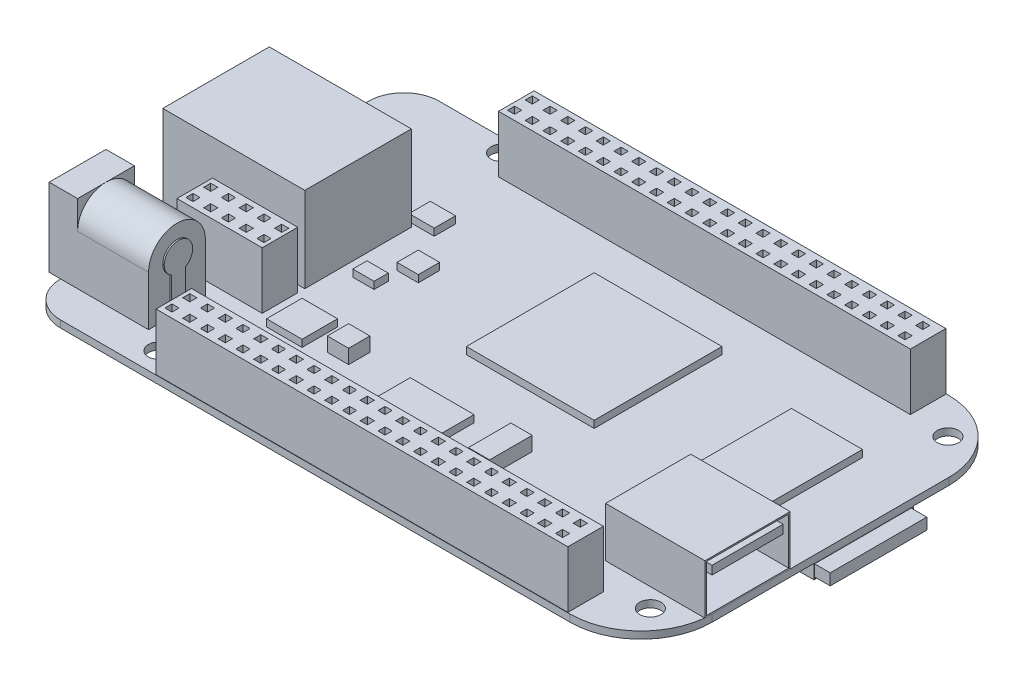
SolidWorks part; units mm, degrees
material "ABS"
ref_plane "Front" through (0, 0, 0) normal (0, 0, 1) x (1, 0, 0)
ref_plane "Top" through (0, 0, 0) normal (0, 1, 0) x (1, 0, 0)
ref_plane "Right" through (0, 0, 0) normal (1, 0, 0) x (0, 0, -1)
sketch "Sketch1" plane through (0, 0, 0) normal (0, 1, 0) x (1, 0, 0)
  line L0 (-38.5707, -26.67) -> (33.18, -26.67)
  line L1 (-27.8969, -23.495) -> (-27.8969, 24.765) construction
  line L2 (43.18, -16.67) -> (43.18, 16.67)
  line L3 (33.18, 26.67) -> (-38.5707, 26.67)
  line L4 (-43.5707, 21.67) -> (-43.5707, -21.67)
  line L5 (-27.8969, 24.765) -> (38.1431, 24.765) construction
  line L6 (38.1431, 24.765) -> (38.1431, 21.59) construction
  line L7 (-27.8969, -23.495) -> (38.1431, -23.495) construction
  line L8 (38.1431, -23.495) -> (38.1431, -20.32) construction
  arc A0 (43.18, 16.67) -> (33.18, 26.67) centre (33.18, 16.67) ccw
  arc A1 (33.18, -26.67) -> (43.18, -16.67) centre (33.18, -16.67) ccw
  arc A2 (-38.5707, -26.67) -> (-43.5707, -21.67) centre (-38.5707, -21.67) cw
  arc A3 (-43.5707, 21.67) -> (-38.5707, 26.67) centre (-38.5707, 21.67) cw
  circle A4 centre (38.1431, -20.32) radius 1.5
  circle A5 centre (38.1431, 21.59) radius 1.5
  circle A6 centre (-27.8969, -23.495) radius 1.5
  circle A7 centre (-27.8969, 24.765) radius 1.5
  dimension "D1" = 5
  dimension "D5" = 66.04
  dimension "D2" = 48.26
  dimension "D3" = 66.04
  dimension "D4" = 3.175
  dimension "D6" = 3.175
  dimension "D7" = 3.175
extrude "Boss-Extrude3" add sketch "Sketch1" along normal blind 1
sketch "Sketch2" plane through (0, 1, 0) normal (0, 1, 0) x (1, 0, 0)
  line L0 (-25.18, -6.67) -> (-37.18, -6.67)
  line L1 (-25.18, -6.67) -> (-25.18, -11.67)
  line L2 (32.82, -26.62) -> (-25.18, -26.62)
  line L3 (-37.18, -6.67) -> (-37.18, -11.67)
  line L4 (-37.18, -11.67) -> (-25.18, -11.67)
  line L5 (-25.18, -26.62) -> (-25.18, -21.62)
  line L8 (-25.18, -21.62) -> (32.82, -21.62)
  line L9 (32.82, -21.62) -> (32.82, -26.62)
  line L12 (-25.18, 26.62) -> (-25.18, 21.62)
  line L13 (32.82, 26.62) -> (-25.18, 26.62)
  line L14 (32.82, 21.62) -> (32.82, 26.62)
  line L15 (-25.18, 21.62) -> (32.82, 21.62)
extrude "Boss-Extrude5" add sketch "Sketch2" along normal blind 8
sketch "Sketch3" plane through (0, 9, 0) normal (0, 1, 0) x (1, 0, 0)
  line L3 (-22.18, 25.87) -> (-21.18, 25.87)
  line L4 (-22.18, -22.37) -> (-21.18, -22.37)
  line L5 (-24.68, 25.87) -> (-23.68, 25.87)
  line L6 (-21.18, 25.87) -> (-21.18, 24.87)
  line L7 (-23.68, 25.87) -> (-23.68, 24.87)
  line L8 (-23.68, 24.87) -> (-24.68, 24.87)
  line L9 (-24.68, 24.87) -> (-24.68, 25.87)
  line L10 (-21.18, 24.87) -> (-22.18, 24.87)
  line L11 (-22.18, 24.87) -> (-22.18, 25.87)
  line L12 (-19.68, 25.87) -> (-18.68, 25.87)
  line L13 (-18.68, 25.87) -> (-18.68, 24.87)
  line L14 (-18.68, 24.87) -> (-19.68, 24.87)
  line L15 (-19.68, 24.87) -> (-19.68, 25.87)
  line L16 (-17.18, 25.87) -> (-16.18, 25.87)
  line L17 (-16.18, 25.87) -> (-16.18, 24.87)
  line L18 (-16.18, 24.87) -> (-17.18, 24.87)
  line L19 (-17.18, 24.87) -> (-17.18, 25.87)
  line L20 (-14.68, 25.87) -> (-13.68, 25.87)
  line L21 (-13.68, 25.87) -> (-13.68, 24.87)
  line L22 (-13.68, 24.87) -> (-14.68, 24.87)
  line L23 (-14.68, 24.87) -> (-14.68, 25.87)
  line L24 (-12.18, 25.87) -> (-11.18, 25.87)
  line L25 (-11.18, 25.87) -> (-11.18, 24.87)
  line L26 (-11.18, 24.87) -> (-12.18, 24.87)
  line L27 (-12.18, 24.87) -> (-12.18, 25.87)
  line L28 (-9.68, 25.87) -> (-8.68, 25.87)
  line L29 (-8.68, 25.87) -> (-8.68, 24.87)
  line L30 (-8.68, 24.87) -> (-9.68, 24.87)
  line L31 (-9.68, 24.87) -> (-9.68, 25.87)
  line L32 (-7.18, 25.87) -> (-6.18, 25.87)
  line L33 (-6.18, 25.87) -> (-6.18, 24.87)
  line L34 (-6.18, 24.87) -> (-7.18, 24.87)
  line L35 (-7.18, 24.87) -> (-7.18, 25.87)
  line L36 (-4.68, 25.87) -> (-3.68, 25.87)
  line L37 (-3.68, 25.87) -> (-3.68, 24.87)
  line L38 (-3.68, 24.87) -> (-4.68, 24.87)
  line L39 (-4.68, 24.87) -> (-4.68, 25.87)
  line L40 (-2.18, 25.87) -> (-1.18, 25.87)
  line L41 (-1.18, 25.87) -> (-1.18, 24.87)
  line L42 (-1.18, 24.87) -> (-2.18, 24.87)
  line L43 (-2.18, 24.87) -> (-2.18, 25.87)
  line L44 (0.32, 25.87) -> (1.32, 25.87)
  line L45 (1.32, 25.87) -> (1.32, 24.87)
  line L46 (1.32, 24.87) -> (0.32, 24.87)
  line L47 (0.32, 24.87) -> (0.32, 25.87)
  line L48 (2.82, 25.87) -> (3.82, 25.87)
  line L49 (3.82, 25.87) -> (3.82, 24.87)
  line L50 (3.82, 24.87) -> (2.82, 24.87)
  line L51 (2.82, 24.87) -> (2.82, 25.87)
  line L52 (5.32, 25.87) -> (6.32, 25.87)
  line L53 (6.32, 25.87) -> (6.32, 24.87)
  line L54 (6.32, 24.87) -> (5.32, 24.87)
  line L55 (5.32, 24.87) -> (5.32, 25.87)
  line L56 (7.82, 25.87) -> (8.82, 25.87)
  line L57 (8.82, 25.87) -> (8.82, 24.87)
  line L58 (8.82, 24.87) -> (7.82, 24.87)
  line L59 (7.82, 24.87) -> (7.82, 25.87)
  line L60 (10.32, 25.87) -> (11.32, 25.87)
  line L61 (11.32, 25.87) -> (11.32, 24.87)
  line L62 (11.32, 24.87) -> (10.32, 24.87)
  line L63 (10.32, 24.87) -> (10.32, 25.87)
  line L64 (12.82, 25.87) -> (13.82, 25.87)
  line L65 (13.82, 25.87) -> (13.82, 24.87)
  line L66 (13.82, 24.87) -> (12.82, 24.87)
  line L67 (12.82, 24.87) -> (12.82, 25.87)
  line L68 (15.32, 25.87) -> (16.32, 25.87)
  line L69 (16.32, 25.87) -> (16.32, 24.87)
  line L70 (16.32, 24.87) -> (15.32, 24.87)
  line L71 (15.32, 24.87) -> (15.32, 25.87)
  line L72 (17.82, 25.87) -> (18.82, 25.87)
  line L73 (18.82, 25.87) -> (18.82, 24.87)
  line L74 (18.82, 24.87) -> (17.82, 24.87)
  line L75 (17.82, 24.87) -> (17.82, 25.87)
  line L76 (20.32, 25.87) -> (21.32, 25.87)
  line L77 (21.32, 25.87) -> (21.32, 24.87)
  line L78 (21.32, 24.87) -> (20.32, 24.87)
  line L79 (20.32, 24.87) -> (20.32, 25.87)
  line L80 (22.82, 25.87) -> (23.82, 25.87)
  line L81 (23.82, 25.87) -> (23.82, 24.87)
  line L82 (23.82, 24.87) -> (22.82, 24.87)
  line L83 (22.82, 24.87) -> (22.82, 25.87)
  line L84 (25.32, 25.87) -> (26.32, 25.87)
  line L85 (26.32, 25.87) -> (26.32, 24.87)
  line L86 (26.32, 24.87) -> (25.32, 24.87)
  line L87 (25.32, 24.87) -> (25.32, 25.87)
  line L88 (27.82, 25.87) -> (28.82, 25.87)
  line L89 (28.82, 25.87) -> (28.82, 24.87)
  line L90 (28.82, 24.87) -> (27.82, 24.87)
  line L91 (27.82, 24.87) -> (27.82, 25.87)
  line L92 (30.32, 25.87) -> (31.32, 25.87)
  line L93 (31.32, 25.87) -> (31.32, 24.87)
  line L94 (31.32, 24.87) -> (30.32, 24.87)
  line L95 (30.32, 24.87) -> (30.32, 25.87)
  line L96 (-18.68, 23.37) -> (-19.68, 23.37)
  line L97 (-21.18, 23.37) -> (-22.18, 23.37)
  line L98 (-23.68, 23.37) -> (-24.68, 23.37)
  line L99 (31.32, 23.37) -> (30.32, 23.37)
  line L100 (28.82, 23.37) -> (27.82, 23.37)
  line L101 (26.32, 23.37) -> (25.32, 23.37)
  line L102 (23.82, 23.37) -> (22.82, 23.37)
  line L103 (21.32, 23.37) -> (20.32, 23.37)
  line L104 (18.82, 23.37) -> (17.82, 23.37)
  line L105 (16.32, 23.37) -> (15.32, 23.37)
  line L106 (13.82, 23.37) -> (12.82, 23.37)
  line L107 (11.32, 23.37) -> (10.32, 23.37)
  line L108 (8.82, 23.37) -> (7.82, 23.37)
  line L109 (6.32, 23.37) -> (5.32, 23.37)
  line L110 (3.82, 23.37) -> (2.82, 23.37)
  line L111 (1.32, 23.37) -> (0.32, 23.37)
  line L112 (-1.18, 23.37) -> (-2.18, 23.37)
  line L113 (-3.68, 23.37) -> (-4.68, 23.37)
  line L114 (-6.18, 23.37) -> (-7.18, 23.37)
  line L115 (-8.68, 23.37) -> (-9.68, 23.37)
  line L116 (-11.18, 23.37) -> (-12.18, 23.37)
  line L117 (-13.68, 23.37) -> (-14.68, 23.37)
  line L118 (-16.18, 23.37) -> (-17.18, 23.37)
  line L119 (30.32, 23.37) -> (30.32, 22.37)
  line L120 (31.32, 22.37) -> (31.32, 23.37)
  line L121 (30.32, 22.37) -> (31.32, 22.37)
  line L122 (27.82, 23.37) -> (27.82, 22.37)
  line L123 (28.82, 22.37) -> (28.82, 23.37)
  line L124 (27.82, 22.37) -> (28.82, 22.37)
  line L125 (25.32, 23.37) -> (25.32, 22.37)
  line L126 (26.32, 22.37) -> (26.32, 23.37)
  line L127 (25.32, 22.37) -> (26.32, 22.37)
  line L128 (22.82, 23.37) -> (22.82, 22.37)
  line L129 (23.82, 22.37) -> (23.82, 23.37)
  line L130 (22.82, 22.37) -> (23.82, 22.37)
  line L131 (20.32, 23.37) -> (20.32, 22.37)
  line L132 (21.32, 22.37) -> (21.32, 23.37)
  line L133 (20.32, 22.37) -> (21.32, 22.37)
  line L134 (17.82, 23.37) -> (17.82, 22.37)
  line L135 (18.82, 22.37) -> (18.82, 23.37)
  line L136 (17.82, 22.37) -> (18.82, 22.37)
  line L137 (15.32, 23.37) -> (15.32, 22.37)
  line L138 (16.32, 22.37) -> (16.32, 23.37)
  line L139 (15.32, 22.37) -> (16.32, 22.37)
  line L140 (12.82, 23.37) -> (12.82, 22.37)
  line L141 (13.82, 22.37) -> (13.82, 23.37)
  line L142 (12.82, 22.37) -> (13.82, 22.37)
  line L143 (10.32, 23.37) -> (10.32, 22.37)
  line L144 (11.32, 22.37) -> (11.32, 23.37)
  line L145 (10.32, 22.37) -> (11.32, 22.37)
  line L146 (7.82, 23.37) -> (7.82, 22.37)
  line L147 (8.82, 22.37) -> (8.82, 23.37)
  line L148 (7.82, 22.37) -> (8.82, 22.37)
  line L149 (5.32, 23.37) -> (5.32, 22.37)
  line L150 (6.32, 22.37) -> (6.32, 23.37)
  line L151 (5.32, 22.37) -> (6.32, 22.37)
  line L152 (2.82, 23.37) -> (2.82, 22.37)
  line L153 (3.82, 22.37) -> (3.82, 23.37)
  line L154 (2.82, 22.37) -> (3.82, 22.37)
  line L155 (0.32, 23.37) -> (0.32, 22.37)
  line L156 (1.32, 22.37) -> (1.32, 23.37)
  line L157 (0.32, 22.37) -> (1.32, 22.37)
  line L158 (-2.18, 23.37) -> (-2.18, 22.37)
  line L159 (-1.18, 22.37) -> (-1.18, 23.37)
  line L160 (-2.18, 22.37) -> (-1.18, 22.37)
  line L161 (-4.68, 23.37) -> (-4.68, 22.37)
  line L162 (-3.68, 22.37) -> (-3.68, 23.37)
  line L163 (-4.68, 22.37) -> (-3.68, 22.37)
  line L164 (-7.18, 23.37) -> (-7.18, 22.37)
  line L165 (-6.18, 22.37) -> (-6.18, 23.37)
  line L166 (-7.18, 22.37) -> (-6.18, 22.37)
  line L167 (-9.68, 23.37) -> (-9.68, 22.37)
  line L168 (-8.68, 22.37) -> (-8.68, 23.37)
  line L169 (-9.68, 22.37) -> (-8.68, 22.37)
  line L170 (-12.18, 23.37) -> (-12.18, 22.37)
  line L171 (-11.18, 22.37) -> (-11.18, 23.37)
  line L172 (-12.18, 22.37) -> (-11.18, 22.37)
  line L173 (-14.68, 23.37) -> (-14.68, 22.37)
  line L174 (-13.68, 22.37) -> (-13.68, 23.37)
  line L175 (-14.68, 22.37) -> (-13.68, 22.37)
  line L176 (-17.18, 23.37) -> (-17.18, 22.37)
  line L177 (-16.18, 22.37) -> (-16.18, 23.37)
  line L178 (-17.18, 22.37) -> (-16.18, 22.37)
  line L179 (-19.68, 23.37) -> (-19.68, 22.37)
  line L180 (-18.68, 22.37) -> (-18.68, 23.37)
  line L181 (-19.68, 22.37) -> (-18.68, 22.37)
  line L182 (-22.18, 23.37) -> (-22.18, 22.37)
  line L183 (-24.68, 23.37) -> (-24.68, 22.37)
  line L184 (-23.68, 22.37) -> (-23.68, 23.37)
  line L185 (-21.18, 22.37) -> (-21.18, 23.37)
  line L186 (-24.68, 22.37) -> (-23.68, 22.37)
  line L187 (-22.18, 22.37) -> (-21.18, 22.37)
  line L188 (-24.68, -22.37) -> (-23.68, -22.37)
  line L189 (-21.18, -22.37) -> (-21.18, -23.37)
  line L190 (-23.68, -22.37) -> (-23.68, -23.37)
  line L191 (-24.68, -23.37) -> (-24.68, -22.37)
  line L192 (-22.18, -23.37) -> (-22.18, -22.37)
  line L193 (-19.68, -22.37) -> (-18.68, -22.37)
  line L194 (-18.68, -22.37) -> (-18.68, -23.37)
  line L195 (-19.68, -23.37) -> (-19.68, -22.37)
  line L196 (-17.18, -22.37) -> (-16.18, -22.37)
  line L197 (-16.18, -22.37) -> (-16.18, -23.37)
  line L198 (-17.18, -23.37) -> (-17.18, -22.37)
  line L199 (-14.68, -22.37) -> (-13.68, -22.37)
  line L200 (-13.68, -22.37) -> (-13.68, -23.37)
  line L201 (-14.68, -23.37) -> (-14.68, -22.37)
  line L202 (-12.18, -22.37) -> (-11.18, -22.37)
  line L203 (-11.18, -22.37) -> (-11.18, -23.37)
  line L204 (-12.18, -23.37) -> (-12.18, -22.37)
  line L205 (-9.68, -22.37) -> (-8.68, -22.37)
  line L206 (-8.68, -22.37) -> (-8.68, -23.37)
  line L207 (-9.68, -23.37) -> (-9.68, -22.37)
  line L208 (-7.18, -22.37) -> (-6.18, -22.37)
  line L209 (-6.18, -22.37) -> (-6.18, -23.37)
  line L210 (-7.18, -23.37) -> (-7.18, -22.37)
  line L211 (-4.68, -22.37) -> (-3.68, -22.37)
  line L212 (-3.68, -22.37) -> (-3.68, -23.37)
  line L213 (-4.68, -23.37) -> (-4.68, -22.37)
  line L214 (-2.18, -22.37) -> (-1.18, -22.37)
  line L215 (-1.18, -22.37) -> (-1.18, -23.37)
  line L216 (-2.18, -23.37) -> (-2.18, -22.37)
  line L217 (0.32, -22.37) -> (1.32, -22.37)
  line L218 (1.32, -22.37) -> (1.32, -23.37)
  line L219 (0.32, -23.37) -> (0.32, -22.37)
  line L220 (2.82, -22.37) -> (3.82, -22.37)
  line L221 (3.82, -22.37) -> (3.82, -23.37)
  line L222 (2.82, -23.37) -> (2.82, -22.37)
  line L223 (5.32, -22.37) -> (6.32, -22.37)
  line L224 (6.32, -22.37) -> (6.32, -23.37)
  line L225 (5.32, -23.37) -> (5.32, -22.37)
  line L226 (7.82, -22.37) -> (8.82, -22.37)
  line L227 (8.82, -22.37) -> (8.82, -23.37)
  line L228 (7.82, -23.37) -> (7.82, -22.37)
  line L229 (10.32, -22.37) -> (11.32, -22.37)
  line L230 (11.32, -22.37) -> (11.32, -23.37)
  line L231 (10.32, -23.37) -> (10.32, -22.37)
  line L232 (12.82, -22.37) -> (13.82, -22.37)
  line L233 (13.82, -22.37) -> (13.82, -23.37)
  line L234 (12.82, -23.37) -> (12.82, -22.37)
  line L235 (15.32, -22.37) -> (16.32, -22.37)
  line L236 (16.32, -22.37) -> (16.32, -23.37)
  line L237 (15.32, -23.37) -> (15.32, -22.37)
  line L238 (17.82, -22.37) -> (18.82, -22.37)
  line L239 (18.82, -22.37) -> (18.82, -23.37)
  line L240 (17.82, -23.37) -> (17.82, -22.37)
  line L241 (20.32, -22.37) -> (21.32, -22.37)
  line L242 (21.32, -22.37) -> (21.32, -23.37)
  line L243 (20.32, -23.37) -> (20.32, -22.37)
  line L244 (22.82, -22.37) -> (23.82, -22.37)
  line L245 (23.82, -22.37) -> (23.82, -23.37)
  line L246 (22.82, -23.37) -> (22.82, -22.37)
  line L247 (25.32, -22.37) -> (26.32, -22.37)
  line L248 (26.32, -22.37) -> (26.32, -23.37)
  line L249 (25.32, -23.37) -> (25.32, -22.37)
  line L250 (27.82, -22.37) -> (28.82, -22.37)
  line L251 (28.82, -22.37) -> (28.82, -23.37)
  line L252 (27.82, -23.37) -> (27.82, -22.37)
  line L253 (30.32, -22.37) -> (31.32, -22.37)
  line L254 (31.32, -22.37) -> (31.32, -23.37)
  line L255 (30.32, -23.37) -> (30.32, -22.37)
  line L256 (-16.18, -23.37) -> (-17.18, -23.37)
  line L257 (-13.68, -23.37) -> (-14.68, -23.37)
  line L258 (-11.18, -23.37) -> (-12.18, -23.37)
  line L259 (-8.68, -23.37) -> (-9.68, -23.37)
  line L260 (-6.18, -23.37) -> (-7.18, -23.37)
  line L261 (-3.68, -23.37) -> (-4.68, -23.37)
  line L262 (-1.18, -23.37) -> (-2.18, -23.37)
  line L263 (1.32, -23.37) -> (0.32, -23.37)
  line L264 (3.82, -23.37) -> (2.82, -23.37)
  line L265 (6.32, -23.37) -> (5.32, -23.37)
  line L266 (8.82, -23.37) -> (7.82, -23.37)
  line L267 (11.32, -23.37) -> (10.32, -23.37)
  line L268 (13.82, -23.37) -> (12.82, -23.37)
  line L269 (16.32, -23.37) -> (15.32, -23.37)
  line L270 (18.82, -23.37) -> (17.82, -23.37)
  line L271 (21.32, -23.37) -> (20.32, -23.37)
  line L272 (23.82, -23.37) -> (22.82, -23.37)
  line L273 (26.32, -23.37) -> (25.32, -23.37)
  line L274 (28.82, -23.37) -> (27.82, -23.37)
  line L275 (31.32, -23.37) -> (30.32, -23.37)
  line L276 (-23.68, -23.37) -> (-24.68, -23.37)
  line L277 (-21.18, -23.37) -> (-22.18, -23.37)
  line L278 (-18.68, -23.37) -> (-19.68, -23.37)
  line L279 (30.32, -24.87) -> (30.32, -25.87)
  line L280 (31.32, -24.87) -> (30.32, -24.87)
  line L281 (31.32, -25.87) -> (31.32, -24.87)
  line L282 (30.32, -25.87) -> (31.32, -25.87)
  line L283 (27.82, -24.87) -> (27.82, -25.87)
  line L284 (28.82, -24.87) -> (27.82, -24.87)
  line L285 (28.82, -25.87) -> (28.82, -24.87)
  line L286 (27.82, -25.87) -> (28.82, -25.87)
  line L287 (25.32, -24.87) -> (25.32, -25.87)
  line L288 (26.32, -24.87) -> (25.32, -24.87)
  line L289 (26.32, -25.87) -> (26.32, -24.87)
  line L290 (25.32, -25.87) -> (26.32, -25.87)
  line L291 (22.82, -24.87) -> (22.82, -25.87)
  line L292 (23.82, -24.87) -> (22.82, -24.87)
  line L293 (23.82, -25.87) -> (23.82, -24.87)
  line L294 (22.82, -25.87) -> (23.82, -25.87)
  line L295 (20.32, -24.87) -> (20.32, -25.87)
  line L296 (21.32, -24.87) -> (20.32, -24.87)
  line L297 (21.32, -25.87) -> (21.32, -24.87)
  line L298 (20.32, -25.87) -> (21.32, -25.87)
  line L299 (17.82, -24.87) -> (17.82, -25.87)
  line L300 (18.82, -24.87) -> (17.82, -24.87)
  line L301 (18.82, -25.87) -> (18.82, -24.87)
  line L302 (17.82, -25.87) -> (18.82, -25.87)
  line L303 (15.32, -24.87) -> (15.32, -25.87)
  line L304 (16.32, -24.87) -> (15.32, -24.87)
  line L305 (16.32, -25.87) -> (16.32, -24.87)
  line L306 (15.32, -25.87) -> (16.32, -25.87)
  line L307 (12.82, -24.87) -> (12.82, -25.87)
  line L308 (13.82, -24.87) -> (12.82, -24.87)
  line L309 (13.82, -25.87) -> (13.82, -24.87)
  line L310 (12.82, -25.87) -> (13.82, -25.87)
  line L311 (10.32, -24.87) -> (10.32, -25.87)
  line L312 (11.32, -24.87) -> (10.32, -24.87)
  line L313 (11.32, -25.87) -> (11.32, -24.87)
  line L314 (10.32, -25.87) -> (11.32, -25.87)
  line L315 (7.82, -24.87) -> (7.82, -25.87)
  line L316 (8.82, -24.87) -> (7.82, -24.87)
  line L317 (8.82, -25.87) -> (8.82, -24.87)
  line L318 (7.82, -25.87) -> (8.82, -25.87)
  line L319 (5.32, -24.87) -> (5.32, -25.87)
  line L320 (6.32, -24.87) -> (5.32, -24.87)
  line L321 (6.32, -25.87) -> (6.32, -24.87)
  line L322 (5.32, -25.87) -> (6.32, -25.87)
  line L323 (2.82, -24.87) -> (2.82, -25.87)
  line L324 (3.82, -24.87) -> (2.82, -24.87)
  line L325 (3.82, -25.87) -> (3.82, -24.87)
  line L326 (2.82, -25.87) -> (3.82, -25.87)
  line L327 (0.32, -24.87) -> (0.32, -25.87)
  line L328 (1.32, -24.87) -> (0.32, -24.87)
  line L329 (1.32, -25.87) -> (1.32, -24.87)
  line L330 (0.32, -25.87) -> (1.32, -25.87)
  line L331 (-2.18, -24.87) -> (-2.18, -25.87)
  line L332 (-1.18, -24.87) -> (-2.18, -24.87)
  line L333 (-1.18, -25.87) -> (-1.18, -24.87)
  line L334 (-2.18, -25.87) -> (-1.18, -25.87)
  line L335 (-4.68, -24.87) -> (-4.68, -25.87)
  line L336 (-3.68, -24.87) -> (-4.68, -24.87)
  line L337 (-3.68, -25.87) -> (-3.68, -24.87)
  line L338 (-4.68, -25.87) -> (-3.68, -25.87)
  line L339 (-7.18, -24.87) -> (-7.18, -25.87)
  line L340 (-6.18, -24.87) -> (-7.18, -24.87)
  line L341 (-6.18, -25.87) -> (-6.18, -24.87)
  line L342 (-7.18, -25.87) -> (-6.18, -25.87)
  line L343 (-9.68, -24.87) -> (-9.68, -25.87)
  line L344 (-8.68, -24.87) -> (-9.68, -24.87)
  line L345 (-8.68, -25.87) -> (-8.68, -24.87)
  line L346 (-9.68, -25.87) -> (-8.68, -25.87)
  line L347 (-12.18, -24.87) -> (-12.18, -25.87)
  line L348 (-11.18, -24.87) -> (-12.18, -24.87)
  line L349 (-11.18, -25.87) -> (-11.18, -24.87)
  line L350 (-12.18, -25.87) -> (-11.18, -25.87)
  line L351 (-14.68, -24.87) -> (-14.68, -25.87)
  line L352 (-13.68, -24.87) -> (-14.68, -24.87)
  line L353 (-13.68, -25.87) -> (-13.68, -24.87)
  line L354 (-14.68, -25.87) -> (-13.68, -25.87)
  line L355 (-17.18, -24.87) -> (-17.18, -25.87)
  line L356 (-16.18, -24.87) -> (-17.18, -24.87)
  line L357 (-16.18, -25.87) -> (-16.18, -24.87)
  line L358 (-17.18, -25.87) -> (-16.18, -25.87)
  line L359 (-19.68, -24.87) -> (-19.68, -25.87)
  line L360 (-18.68, -24.87) -> (-19.68, -24.87)
  line L361 (-18.68, -25.87) -> (-18.68, -24.87)
  line L362 (-19.68, -25.87) -> (-18.68, -25.87)
  line L363 (-22.18, -24.87) -> (-22.18, -25.87)
  line L364 (-21.18, -24.87) -> (-22.18, -24.87)
  line L365 (-24.68, -24.87) -> (-24.68, -25.87)
  line L366 (-23.68, -24.87) -> (-24.68, -24.87)
  line L367 (-23.68, -25.87) -> (-23.68, -24.87)
  line L368 (-21.18, -25.87) -> (-21.18, -24.87)
  line L369 (-24.68, -25.87) -> (-23.68, -25.87)
  line L370 (-22.18, -25.87) -> (-21.18, -25.87)
  line L371 (-28.18, -10.92) -> (-29.18, -10.92)
  line L410 (-25.68, -10.92) -> (-26.68, -10.92)
  line L411 (-29.18, -10.92) -> (-29.18, -9.92)
  line L412 (-26.68, -10.92) -> (-26.68, -9.92)
  line L413 (-25.68, -9.92) -> (-25.68, -10.92)
  line L414 (-28.18, -9.92) -> (-28.18, -10.92)
  line L415 (-30.68, -10.92) -> (-31.68, -10.92)
  line L416 (-31.68, -10.92) -> (-31.68, -9.92)
  line L417 (-30.68, -9.92) -> (-30.68, -10.92)
  line L418 (-33.18, -10.92) -> (-34.18, -10.92)
  line L419 (-34.18, -10.92) -> (-34.18, -9.92)
  line L420 (-33.18, -9.92) -> (-33.18, -10.92)
  line L421 (-35.68, -10.92) -> (-36.68, -10.92)
  line L422 (-36.68, -10.92) -> (-36.68, -9.92)
  line L423 (-35.68, -9.92) -> (-35.68, -10.92)
  line L424 (-34.18, -9.92) -> (-33.18, -9.92)
  line L425 (-36.68, -9.92) -> (-35.68, -9.92)
  line L426 (-26.68, -9.92) -> (-25.68, -9.92)
  line L427 (-29.18, -9.92) -> (-28.18, -9.92)
  line L428 (-31.68, -9.92) -> (-30.68, -9.92)
  line L429 (-35.68, -8.42) -> (-35.68, -7.42)
  line L430 (-36.68, -8.42) -> (-35.68, -8.42)
  line L431 (-36.68, -7.42) -> (-36.68, -8.42)
  line L432 (-35.68, -7.42) -> (-36.68, -7.42)
  line L433 (-33.18, -8.42) -> (-33.18, -7.42)
  line L434 (-34.18, -8.42) -> (-33.18, -8.42)
  line L435 (-34.18, -7.42) -> (-34.18, -8.42)
  line L436 (-33.18, -7.42) -> (-34.18, -7.42)
  line L437 (-30.68, -8.42) -> (-30.68, -7.42)
  line L438 (-31.68, -8.42) -> (-30.68, -8.42)
  line L439 (-31.68, -7.42) -> (-31.68, -8.42)
  line L440 (-30.68, -7.42) -> (-31.68, -7.42)
  line L441 (-28.18, -8.42) -> (-28.18, -7.42)
  line L442 (-29.18, -8.42) -> (-28.18, -8.42)
  line L443 (-25.68, -8.42) -> (-25.68, -7.42)
  line L444 (-26.68, -8.42) -> (-25.68, -8.42)
  line L445 (-26.68, -7.42) -> (-26.68, -8.42)
  line L446 (-29.18, -7.42) -> (-29.18, -8.42)
  line L447 (-25.68, -7.42) -> (-26.68, -7.42)
  line L448 (-28.18, -7.42) -> (-29.18, -7.42)
  dimension "D1" = 23
extrude "Cut-Extrude2" cut sketch "Sketch3" against normal blind 7
sketch "Sketch4" plane through (0, 1, 0) normal (0, 1, 0) x (1, 0, 0)
  line L1 (-25.18, -5.67) -> (-45.18, -5.67)
  line L2 (-45.18, -5.67) -> (-45.18, 9.33)
  line L3 (-45.18, 9.33) -> (-25.18, 9.33)
  line L4 (-25.18, 9.33) -> (-25.18, -5.67)
extrude "Boss-Extrude6" add sketch "Sketch4" along normal blind 12
sketch "Sketch5" plane through (-45.18, 0, 0) normal (-1, 0, 0) x (0, 0, 1)
  line L3 (-4.33, 2) -> (-5.33, 2)
  line L4 (-5.33, 2) -> (-5.33, 4)
  line L5 (-5.33, 4) -> (-8.33, 4)
  line L6 (-8.33, 4) -> (-8.33, 11)
  line L7 (-8.33, 11) -> (4.67, 11)
  line L8 (-4.33, 2) -> (-4.33, 1.05)
  line L9 (0.67, 1.05) -> (0.67, 2)
  line L10 (4.67, 4) -> (4.67, 11)
  line L11 (1.67, 4) -> (4.67, 4)
  line L12 (1.67, 2) -> (1.67, 4)
  line L13 (0.67, 2) -> (1.67, 2)
  line L14 (-4.33, 1.05) -> (0.67, 1.05)
extrude "Cut-Extrude3" cut sketch "Sketch5" against normal blind 15
sketch "Sketch6" plane through (0, 1, 0) normal (0, 1, 0) x (1, 0, 0)
  line L0 (-31.18, -21.67) -> (-31.18, -13.67)
  line L1 (-31.18, -13.67) -> (-45.18, -13.67)
  line L2 (-31.18, -21.67) -> (-45.18, -21.67)
  line L3 (-45.18, -13.67) -> (-45.18, -21.67)
extrude "Boss-Extrude7" add sketch "Sketch6" along normal blind 11
sketch "Sketch8" plane through (-31.18, 0, 0) normal (1, 0, 0) x (0, 0, -1)
  line L1 (-13.67, 8) -> (-13.67, 12)
  line L2 (-13.67, 12) -> (-21.67, 12)
  line L3 (-21.67, 12) -> (-21.67, 8)
  arc A0 (-13.67, 8) -> (-21.67, 8) centre (-17.67, 8) ccw
  line M2 (-13.67, 1) -> (-13.67, 12)
  line M3 (-13.67, 12) -> (-21.67, 12)
  line M4 (-21.67, 12) -> (-21.67, 1)
extrude "Cut-Extrude5" cut sketch "Sketch8" against normal blind 10 contours A0 L2 M4 | A0 M2 M3 region at (-31.18, 11.1065, 14.5635) region at (-31.18, 11.1065, 20.7765)
sketch "Sketch9" plane through (-45.18, 0, 0) normal (-1, 0, 0) x (0, 0, 1)
  circle A0 centre (17.67, 8) radius 3
  circle A1 centre (17.67, 8) radius 0.2
extrude "Cut-Extrude6" cut sketch "Sketch9" against normal blind 10 contours A0 A1 region at (-45.18, 8, 14.7549)
sketch "Sketch10" plane through (0, 1, 0) normal (0, 1, 0) x (1, 0, 0)
  line L0 (43.18, -5.67) -> (29.18, -5.67)
  line L1 (43.18, -16.67) -> (43.18, 16.67) construction
  line L2 (43.18, -5.67) -> (43.18, -17.67)
  line L3 (29.18, -5.67) -> (29.18, -17.67)
  line L4 (29.18, -17.67) -> (43.18, -17.67)
extrude "Boss-Extrude9" add sketch "Sketch10" along normal blind 7 separate body
sketch "Sketch11" plane through (43.18, 0, 0) normal (1, 0, 0) x (0, 0, -1)
  line L0 (-17.47, 7.8) -> (-17.47, 1.2)
  line L1 (-5.87, 7.8) -> (-5.87, 1.2)
  line L3 (-16.67, 6.9526) -> (-16.67, 5.7526)
  line L4 (-16.67, 5.7526) -> (-6.67, 5.7526)
  line L5 (-6.67, 6.9526) -> (-16.67, 6.9526)
  line L6 (-6.67, 5.7526) -> (-6.67, 6.9526)
  line L7 (-17.47, 7.8) -> (-5.87, 7.8)
  line L10 (-17.47, 1.2) -> (-5.87, 1.2)
extrude "Cut-Extrude7" cut sketch "Sketch11" against normal blind 10 contours L0 L10 L1 L7 L6 L4 L3 L5 region at (43.18, 4.1557, 11.67)
sketch "Sketch12" plane through (0, 0, 0) normal (0, -1, 0) x (1, 0, 0)
  line L0 (43.18, 2.33) -> (43.18, -11.67)
  line L1 (43.18, -11.67) -> (28.18, -11.67)
  line L2 (43.18, 16.67) -> (43.18, -16.67) construction
  line L4 (28.18, -11.67) -> (28.18, 2.33)
  line L5 (28.18, 2.33) -> (43.18, 2.33)
extrude "Boss-Extrude11" add sketch "Sketch12" along normal blind 2 separate body
shell "Shell1" thickness 0.1 removed face at (43.18, -1, -4.67)
sketch "Sketch13" plane through (28.28, 0, 0) normal (1, 0, 0) x (0, 0, -1)
  line L0 (-2.13, -0.1927) -> (11.47, -0.1927)
  line L1 (-2.13, -0.1927) -> (-2.13, -1.7927)
  line L4 (11.47, -0.1927) -> (11.47, -1.7927)
  line L5 (-2.13, -1.7927) -> (11.47, -1.7927)
extrude "Boss-Extrude12" add sketch "Sketch13" along normal blind 17
sketch "Sketch14" plane through (0, 1, 0) normal (0, 1, 0) x (1, 0, 0)
  line L1 (12.2441, -2.3365) -> (-5.7559, -2.3365)
  line L2 (12.2441, -2.3365) -> (12.2441, 15.6635)
  line L3 (12.2441, 15.6635) -> (-5.7559, 15.6635)
  line L4 (-5.7559, -2.3365) -> (-5.7559, 15.6635)
  line L5 (34.6895, 0) -> (24.6895, 0)
  line L6 (34.6895, 0) -> (34.6895, 13)
  line L7 (34.6895, 13) -> (24.6895, 13)
  line L8 (24.6895, 0) -> (24.6895, 13)
  line L9 (-26.0056, 12.8416) -> (-22.4654, 12.8416)
  line L10 (-26.0056, 12.8416) -> (-26.0056, 9.8416)
  line L11 (-26.0056, 9.8416) -> (-22.4654, 9.8416)
  line L12 (-22.4654, 12.8416) -> (-22.4654, 9.8416)
  line L13 (-20.9077, 6.0445) -> (-17.9077, 6.0445)
  line L14 (-20.9077, 6.0445) -> (-20.9077, 3.0445)
  line L15 (-20.9077, 3.0445) -> (-17.9077, 3.0445)
  line L16 (-17.9077, 6.0445) -> (-17.9077, 3.0445)
  line L17 (-20.2116, -0.8835) -> (-23.2116, -0.8835)
  line L18 (-20.2116, -0.8835) -> (-20.2116, 1.1165)
  line L19 (-20.2116, 1.1165) -> (-23.2116, 1.1165)
  line L20 (-23.2116, -0.8835) -> (-23.2116, 1.1165)
  line L21 (-5.9069, -10.0954) -> (3.0931, -10.0954)
  line L22 (-5.9069, -10.0954) -> (-5.9069, -19.0954)
  line L23 (-5.9069, -19.0954) -> (3.0931, -19.0954)
  line L24 (3.0931, -10.0954) -> (3.0931, -19.0954)
  line L25 (-23.2116, -8.0248) -> (-18.2116, -8.0248)
  line L26 (-23.2116, -8.0248) -> (-23.2116, -13.0248)
  line L27 (-23.2116, -13.0248) -> (-18.2116, -13.0248)
  line L28 (-18.2116, -8.0248) -> (-18.2116, -13.0248)
extrude "Boss-Extrude13" add sketch "Sketch14" along normal blind 1 separate body
sketch "Sketch15" plane through (0, 0, 0) normal (0, -1, 0) x (1, 0, 0)
  line L0 (-43.5707, -21.67) -> (-35.5707, -21.67)
  line L3 (-35.5707, -21.67) -> (-35.5707, -14.67)
  line L4 (-35.5707, -14.67) -> (-43.5707, -14.67)
  line L5 (-43.5707, -21.67) -> (-43.5707, 21.67) construction
  line L6 (-43.5707, -14.67) -> (-43.5707, -21.67)
extrude "Boss-Extrude14" add sketch "Sketch15" along normal blind 4 separate body
sketch "Sketch16" plane through (-43.5707, 0, 0) normal (-1, 0, 0) x (0, 0, 1)
  line L2 (-21.67, 0) -> (21.67, 0) construction
  line L4 (-21.67, -4) -> (-21.67, 0) construction
  line L5 (-21.67, -0.5) -> (-21.17, 0)
  line L7 (-14.67, -0.5) -> (-15.17, 0)
  line M1 (-14.67, 0) -> (-21.67, 0)
  line M2 (-21.67, 0) -> (-21.67, -4)
  line M4 (-14.67, -4) -> (-14.67, 0)
extrude "Cut-Extrude8" cut sketch "Sketch16" along direction (-1, 0, 0) on the side of the normal through all and the other way through all contours L5 M2 M1 | L7 M4 M1 region at (-43.5707, -0.1667, -21.5033) region at (-43.5707, -0.1667, -14.8367)
shell "Shell2" thickness 0.1 removed face at (-43.5707, -1.5, -18.17)
sketch "Sketch17" plane through (-35.6707, 0, 0) normal (-1, 0, 0) x (0, 0, 1)
  line L0 (-21.075, -1.0364) -> (-21.075, -2.0364)
  line L1 (-21.075, -2.0364) -> (-15.265, -2.0364)
  line L2 (-15.265, -2.0364) -> (-15.265, -1.0364)
  line L3 (-21.075, -1.0364) -> (-20.8386, -0.8)
  line L4 (-20.8386, -0.8) -> (-15.5014, -0.8)
  line L5 (-15.5014, -0.8) -> (-15.265, -1.0364)
extrude "Boss-Extrude15" add sketch "Sketch17" along normal blind 7 separate body
sketch "Sketch18" plane through (-42.6707, 0, 0) normal (-1, 0, 0) x (0, 0, 1)
  circle A0 centre (-20.5492, -1.4683) radius 0.1
  circle A1 centre (-19.3492, -1.4683) radius 0.1
  circle A2 centre (-18.1492, -1.4683) radius 0.1
  circle A3 centre (-16.9492, -1.4683) radius 0.1
  circle A4 centre (-15.7492, -1.4683) radius 0.1
  dimension "D1" = 5
extrude "Cut-Extrude9" cut sketch "Sketch18" against normal blind 6 contours A0 | A1 | A2 | A4 | A3 region at (-42.6707, -1.4683, -20.5492) region at (-42.6707, -1.4683, -19.3492) region at (-42.6707, -1.4683, -18.1492) region at (-42.6707, -1.4683, -15.7492)
sketch "Sketch19" plane through (0, 1, 0) normal (0, 1, 0) x (1, 0, 0)
  line L1 (-19.0972, -16.6436) -> (-16.0972, -16.6436)
  line L2 (-21.6286, -16.6436) -> (-24.6286, -16.6436)
  line L3 (-21.6286, -16.6436) -> (-21.6286, -19.6436)
  line L4 (-21.6286, -19.6436) -> (-24.6286, -19.6436)
  line L5 (-24.6286, -16.6436) -> (-24.6286, -19.6436)
  line L6 (-19.0972, -16.6436) -> (-19.0972, -19.6436)
  line L7 (-19.0972, -19.6436) -> (-16.0972, -19.6436)
  line L8 (-16.0972, -16.6436) -> (-16.0972, -19.6436)
  line L9 (-15.8351, -8.8429) -> (-12.8351, -8.8429)
  line L10 (-15.8351, -8.8429) -> (-15.8351, -11.8429)
  line L11 (-15.8351, -11.8429) -> (-12.8351, -11.8429)
  line L12 (-12.8351, -8.8429) -> (-12.8351, -11.8429)
  line L13 (7.7089, -9.5305) -> (10.7089, -9.5305)
  line L14 (7.7089, -9.5305) -> (7.7089, -15.5305)
  line L15 (7.7089, -15.5305) -> (10.7089, -15.5305)
  line L16 (10.7089, -9.5305) -> (10.7089, -15.5305)
  line L17 (28.0786, -10.0656) -> (26.2944, -10.0656)
  line L18 (28.0786, -10.0656) -> (28.0786, -13.8772)
  line L19 (28.0786, -13.8772) -> (26.2944, -13.8772)
  line L20 (26.2944, -10.0656) -> (26.2944, -13.8772)
extrude "Boss-Extrude17" add sketch "Sketch19" along normal blind 2
sketch "Sketch20" plane through (-31.18, 0, 0) normal (1, 0, 0) x (0, 0, -1)
  line L2 (-18.67, 6.2679) -> (-18.67, 1)
  line L3 (-16.67, 1) -> (-26.67, 1) construction
  line L4 (-16.67, 6.2679) -> (-16.67, 1)
  line L5 (-18.67, 1) -> (-16.67, 1)
  arc A0 (-16.67, 6.2679) -> (-18.67, 6.2679) centre (-17.67, 8) ccw
extrude "Boss-Extrude18" add sketch "Sketch20" along normal blind 0.2
